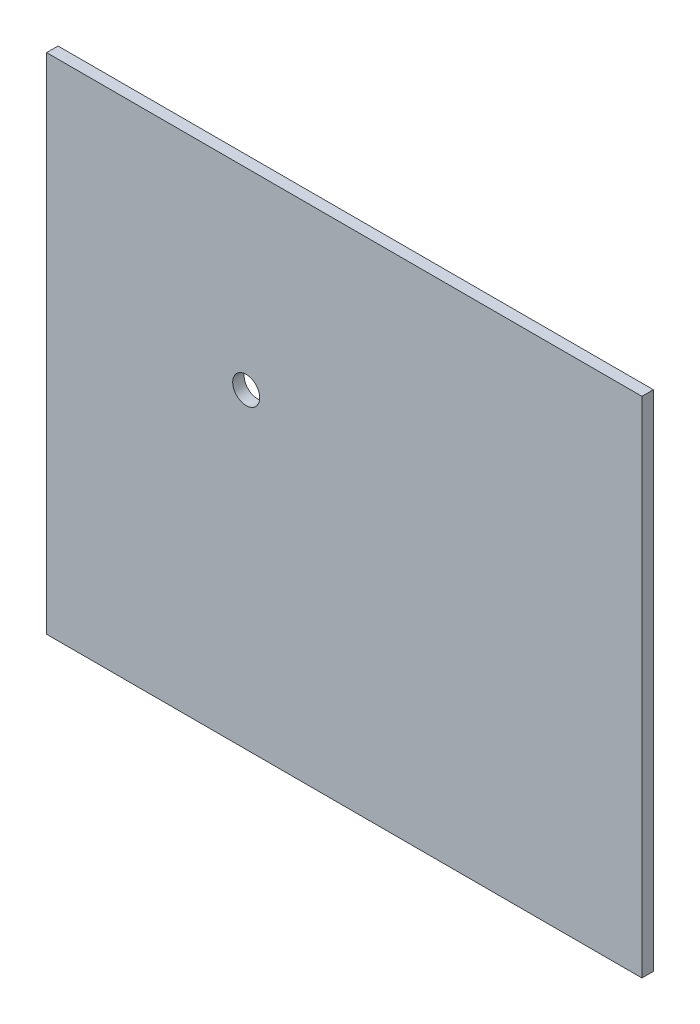
SolidWorks part; units mm, degrees
material "ALUMINUM 6061-T6"
ref_plane "Front Plane" through (0, 0, 0) normal (0, 0, 1) x (1, 0, 0)
ref_plane "Top Plane" through (0, 0, 0) normal (0, 1, 0) x (1, 0, 0)
ref_plane "Right Plane" through (0, 0, 0) normal (1, 0, 0) x (0, 0, -1)
sketch "Sketch1" plane through (0, 0, 0) normal (0, 0, 1) x (1, 0, 0)
  line L1 (-165.1, -139.7) -> (165.1, -139.7)
  line L2 (-165.1, -139.7) -> (-165.1, 139.7)
  line L3 (-165.1, 139.7) -> (165.1, 139.7)
  line L4 (165.1, -139.7) -> (165.1, 139.7)
  line L5 (-165.1, -139.7) -> (165.1, 139.7) construction
  line L6 (-165.1, 139.7) -> (165.1, -139.7) construction
  point P0 (0, 0)
  dimension "D1" = 330.2
  dimension "D2" = 279.4
extrude "Boss-Extrude1" add sketch "Sketch1" along normal mid plane 6.35
hole_wizard "M14 Clearance Hole1" positions "Sketch3" profile "Sketch2" hole size "M14" standard "Lanco STD" end condition through all
sketch "Sketch3" plane through (0, 0, 3.175) normal (0, 0, 1) x (1, 0, 0)
  point P0 (-54.3938, 32.999)
sketch "Sketch2" plane through (-54.3938, 32.999, 3.175) normal (1, 0, 0) x (0, -1, 0)
  line L0 (0, 0) -> (0, 6.35)
  line L1 (0, 6.35) -> (7.5, 6.35)
  line L2 (7.5, 6.35) -> (7.5, 0)
  line L5 (7.5, 0) -> (0, 0)
  line L11 (0, -6.35) -> (0, 107.95) construction
  dimension "Thru Hole Dia." = 15
  dimension "Thru Hole Depth" = 6.35
